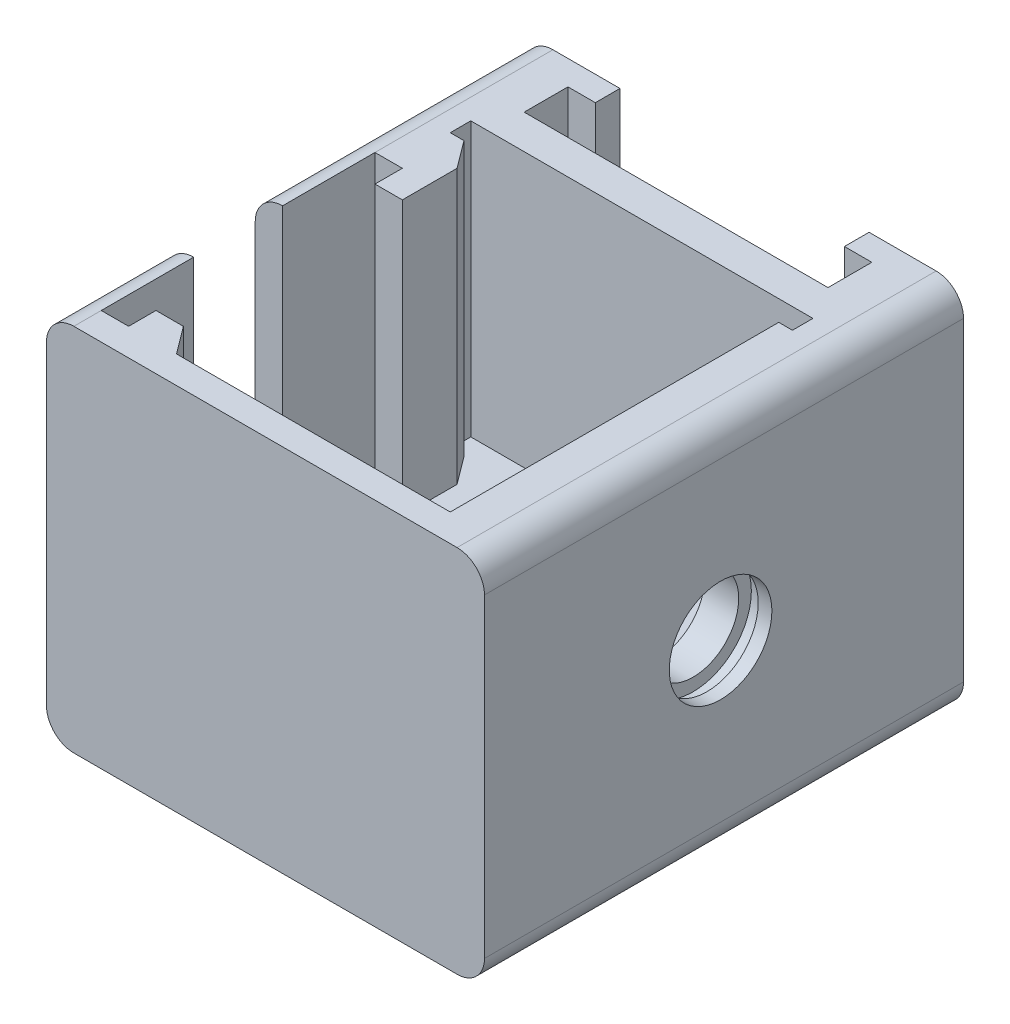
SolidWorks part; units mm, degrees
material "UNOBTANIUM"
ref_plane "Top Plane" through (0, 0, 0) normal (0, 0, 1) x (1, 0, 0)
ref_plane "Right Plane" through (0, 0, 0) normal (0, 1, 0) x (1, 0, 0)
ref_plane "Front Plane" through (0, 0, 0) normal (1, 0, 0) x (0, 0, -1)
ref_axis "x-axis" through (-17.6, 0, 0) along (1, 0, 0)
ref_axis "y-axis" through (0, -14.85, 0) along (0, 1, 0)
ref_axis "z-axis" through (0, 0, 36.75) along (0, 0, -1)
sketch "Sketch1" plane through (0, 0, 0) normal (0, 0, 1) x (1, 0, 0)
  line L1 (-16, 13.5) -> (16, 13.5)
  line L2 (-16, 13.5) -> (-16, -13.5)
  line L3 (-16, -13.5) -> (16, -13.5)
  line L4 (16, 13.5) -> (16, -13.5)
  line L5 (-16, 13.5) -> (16, -13.5) construction
  line L6 (-16, -13.5) -> (16, 13.5) construction
  point P0 (0, 0)
  dimension "D1" = 32
  dimension "D2" = 27
extrude "Boss-Extrude1" add sketch "Sketch1" along normal blind 35
fillet "Fillet1" radius 2 4 edges at (16, -13.5, 17.5) (16, 13.5, 17.5) (-16, -13.5, 17.5) (-16, 13.5, 17.5)
sketch "Sketch2" plane through (0, -13.5, 0) normal (0, -1, 0) x (1, 0, 0)
  line L0 (-9.1, 0) -> (-9.1, 1.8)
  line L1 (-14, 0) -> (14, 0) construction
  line L2 (-9.1, 1.8) -> (-11.1, 1.8)
  line L3 (-11.1, 1.8) -> (-11.1, 5)
  line L4 (-11.1, 5) -> (11.1, 5)
  line L5 (11.1, 5) -> (11.1, 1.8)
  line L6 (11.1, 1.8) -> (9.1, 1.8)
  line L7 (9.1, 1.8) -> (9.1, 0)
  line L9 (-9.1, 0) -> (9.1, 0)
  point P4 (0, 0)
  dimension "D1" = 18.2
  dimension "D2" = 1.8
  dimension "D3" = 3.2
  dimension "D4" = 22.2
extrude "Cut-Extrude1" cut sketch "Sketch2" against normal through all both and the other way through all
sketch "Sketch3" plane through (0, -13.5, 0) normal (0, -1, 0) x (1, 0, 0)
  line L0 (-9.1, 0) -> (-9.1, 1.8)
  line L1 (-9.1, 1.8) -> (-11.1, 1.8)
  line L2 (-11.1, 1.8) -> (-11.1, 5)
  line L3 (-11.1, 5) -> (11.1, 5)
  line L4 (11.1, 5) -> (11.1, 1.8)
  line L5 (11.1, 1.8) -> (9.1, 1.8)
  line L6 (9.1, 1.8) -> (9.1, 0)
  line L7 (9.1, 0) -> (-9.1, 0)
extrude "Boss-Extrude2" add sketch "Sketch3" against normal blind 7
sketch "Sketch4" plane through (0, 0, 1.8) normal (0, 0, -1) x (-1, 0, 0)
  line L1 (-9.1, 6.5) -> (-9.1, 5.5)
  line L2 (-9.1, 13.5) -> (-9.1, -6.5) construction
  arc A0 (-9.1, 6.5) -> (-9.1, 5.5) centre (-9.475, 6) cw
  dimension "D1" = 0.625
  dimension "D2" = 0.25
  dimension "D3" = 7
extrude "Boss-Extrude3" add sketch "Sketch4" along normal up to surface (1.8 mm away) up to face at (0, 1.1667, 0)
mirror "Mirror1" about plane through (0, 0, 0) normal (1, 0, 0) of "Boss-Extrude3"
sketch "Sketch5" plane through (0, 0, 0) normal (0, 0, -1) x (-1, 0, 0)
  line L0 (9.1, -6.5) -> (-9.1, -6.5) construction
  line L1 (-1, -6.5) -> (1, -6.5)
  line L2 (-1, -6.5) -> (-1, -13.5)
  line L3 (-1, -13.5) -> (1, -13.5)
  line L4 (1, -6.5) -> (1, -13.5)
  line L5 (14, -13.5) -> (-14, -13.5) construction
  point P8 (0, -6.5)
  dimension "D1" = 2
extrude "Cut-Extrude2" cut sketch "Sketch5" against normal offset from surface (33 mm away) 2 up to face at (0, 0, 35)
sketch "Sketch6" plane through (0, 13.5, 0) normal (0, 1, 0) x (1, 0, 0)
  line L0 (-12.5, -7.5) -> (-12.5, -9)
  line L1 (-12.5, -9) -> (-11.5, -9)
  line L2 (-11.5, -9) -> (-11.5, -33)
  line L3 (-11.5, -33) -> (11.5, -33)
  line L4 (11.5, -33) -> (11.5, -9)
  line L5 (11.5, -9) -> (12.5, -9)
  line L6 (12.5, -9) -> (12.5, -7.5)
  line L7 (12.5, -7.5) -> (-12.5, -7.5)
  line L8 (11.1, -5) -> (-11.1, -5) construction
  line L9 (0, -7.5) -> (0, -5) construction
  line L10 (14, -35) -> (-14, -35) construction
  dimension "D1" = 2.5
  dimension "D2" = 1.5
  dimension "D3" = 1
  dimension "D4" = 25
  dimension "D5" = 2
extrude "Cut-Extrude3" cut sketch "Sketch6" against normal up to surface (20 mm away) up to face at (7.0667, -6.5, 2.2667)
sketch "Sketch7" plane through (0, -13.5, 0) normal (0, -1, 0) x (1, 0, 0)
  line L0 (1, 0) -> (14, 0) construction
  line L1 (1, 0) -> (-1, 0)
  line L2 (1, 0) -> (1, 33)
  line L3 (1, 33) -> (-1, 33)
  line L4 (-1, 0) -> (-1, 33)
  line L5 (1, 33) -> (1, 0) construction
extrude "Boss-Extrude4" add sketch "Sketch7" against normal blind 0.25
fillet "Fillet2" radius 6 1 edges at (0, -13.25, 33)
ref_axis "Axis1" through (63.07, 0, 17.75) along (-1, 0, 0)
ref_plane "Plane1" through (0, 0, 17.75) normal (0, 0, -1) x (-1, 0, 0)
sketch "Sketch9" plane through (0, 0, 17.75) normal (0, 0, -1) x (-1, 0, 0)
  line L0 (-15, 4.25) -> (-14, 4.25)
  line L1 (-16, -11.5) -> (-16, 11.5) construction
  line L2 (-14, 4.25) -> (-14, 3.325)
  line L3 (-14, 3.325) -> (-11.5, 3.325)
  line L4 (-11.5, 3.325) -> (-11.5, 0)
  line L5 (-63.07, 0) -> (46.93, 0) construction
  line L6 (-11.5, 0) -> (-16, 0)
  line L8 (-16, 0) -> (-0.664, 0) construction
  line L9 (-11.5, -6.5) -> (-11.5, 13.5) construction
  line L10 (-15, 4.25) -> (-15, 3.75)
  line L11 (-15, 3.75) -> (-16, 3.75)
  line L12 (-16, 3.75) -> (-16, 0)
  dimension "D1" = 6.65
  dimension "D2" = 8.5
  dimension "D3" = 1
  dimension "D4" = 1
  dimension "D5" = 7.5
revolve "Cut-Revolve1" cut sketch "Sketch9" angle 360 about L8
sketch "Sketch10" plane through (0, 13.5, 0) normal (0, 1, 0) x (1, 0, 0)
  line L0 (11.5, -31) -> (13.5, -31)
  line L1 (11.5, -9) -> (11.5, -33) construction
  line L2 (13.5, -31) -> (13.5, -33)
  line L3 (13.5, -33) -> (11.5, -33)
  line L4 (11.5, -33) -> (11.5, -31)
  dimension "D1" = 2
  dimension "D2" = 2
extrude "Cut-Extrude4" [suppressed] cut sketch "Sketch10" against normal up to surface (20 mm away)
mirror "Mirror2" [suppressed] about plane through (0, 0, 0) normal (1, 0, 0)
sketch "Sketch11" plane through (-16, 0, 44) normal (1, 0, 0) x (0, 0, -1)
  line L0 (21, 23) -> (21, 0) construction
  line L4 (24.25, 23) -> (24.25, 0)
  line L5 (17.75, 23) -> (17.75, 0)
  line L6 (9, 11.5) -> (44, 11.5) construction
  line L7 (21, 0) -> (44, 0) construction
  line L8 (9, 11.5) -> (9, -11.5) construction
  arc A2 (24.25, 23) -> (17.75, 23) centre (21, 23) ccw
  arc A3 (17.75, 0) -> (24.25, 0) centre (21, 0) ccw
  point P2 (21, 11.5)
  dimension "D1" = 6.5
  dimension "D2" = 12
extrude "Cut-Extrude5" cut sketch "Sketch11" along normal up to surface (4.5 mm away) up to face at (-11.5, 3.5, 21)
sketch "Sketch14" plane through (0, 13.5, 0) normal (0, 1, 0) x (1, 0, 0)
  line L0 (-11.5, -9) -> (-11.5, -19.75) construction
  line L1 (-11.5, -13) -> (-14, -13)
  line L2 (-11.5, -13) -> (-11.5, -33)
  line L3 (-11.5, -33) -> (-14, -33)
  line L4 (-14, -13) -> (-14, -33)
  line L5 (-16, -35) -> (-16, -26.25) construction
  line L6 (-11.5, -26.25) -> (-11.5, -19.75) construction
  point P12 (-11.5, -23)
  dimension "D1" = 2
extrude "Cut-Extrude6" cut sketch "Sketch14" against normal up to surface (20 mm away) up to face at (-8.3333, -6.5, 16.5)
sketch "Sketch16" plane through (0, 13.5, 0) normal (0, 1, 0) x (1, 0, 0)
  line L1 (-12, -11) -> (-10, -11)
  line L2 (-12, -11) -> (-12, -15)
  line L3 (-12, -15) -> (-10, -15)
  line L4 (-10, -11) -> (-10, -15)
  line L5 (-14, -33) -> (-14, -13) construction
  line L6 (-12, -33) -> (-12, -31)
  line L7 (-14, -33) -> (11.5, -33) construction
  line L8 (-12, -31) -> (-10, -31)
  line L9 (-10, -31) -> (-10, -33)
  line L10 (-10, -33) -> (-12, -33)
  line L11 (-12.5, -9) -> (-11.5, -9) construction
  line L13 (-11.5, -13) -> (-14, -13) construction
  line L14 (-14, -13) -> (-14, -19.75) construction
  dimension "D1" = 4
  dimension "D2" = 2
  dimension "D3" = 2
  dimension "D4" = 2
  dimension "D5" = 2
extrude "Boss-Extrude5" add sketch "Sketch16" against normal up to surface (20 mm away) up to face at (8.3333, -6.5, 16.5)
sketch "Sketch20" plane through (0, 13.5, 0) normal (0, 1, 0) x (1, 0, 0)
  line L0 (-11.5, -9) -> (-10, -11)
  line L1 (-10, -11) -> (-11.5, -11)
  line L2 (-11.5, -11) -> (-11.5, -9)
  line L3 (-10, -31) -> (-8.5, -33)
  line L4 (-1, -33) -> (-10, -33) construction
  line L5 (-8.5, -33) -> (-10, -33)
  line L6 (-10, -33) -> (-10, -31)
extrude "Boss-Extrude6" add sketch "Sketch20" against normal up to surface (20 mm away) up to face at (8.3333, -6.5, 16.5)
